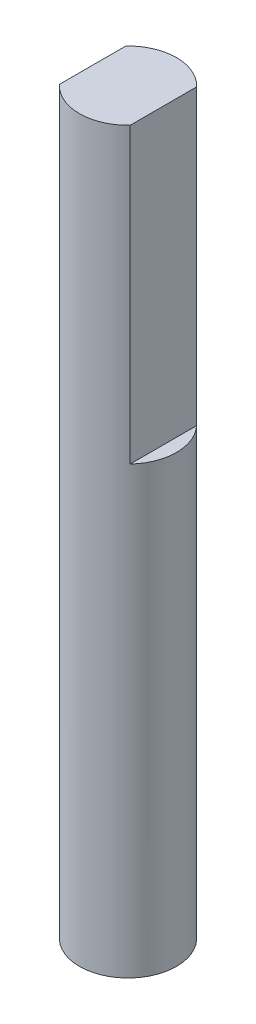
SolidWorks part; units mm, degrees
material "ABS"
ref_plane "Alzado" through (0, 0, 0) normal (0, 0, 1) x (1, 0, 0)
ref_plane "Planta" through (0, 0, 0) normal (0, 1, 0) x (1, 0, 0)
ref_plane "Vista lateral" through (0, 0, 0) normal (1, 0, 0) x (0, 0, -1)
sketch "Croquis2" plane through (0, 0, 0) normal (0, 1, 0) x (1, 0, 0)
  circle A0 centre (0, 0) radius 2.4
  dimension "D1" = 4.8
extrude "Saliente-Extruir1" add sketch "Croquis2" along normal mid plane 36.5
sketch "Croquis3" plane through (0, 18.25, 0) normal (0, 1, 0) x (1, 0, 0)
  line L0 (0, 0) -> (0, 2.4) construction
  line L1 (-1.75, 1.6424) -> (-1.75, -1.6424)
  line L2 (1.75, 1.6424) -> (1.75, -1.6424)
  circle A0 centre (0, 0) radius 2.4 construction
  arc A1 (-1.75, -1.6424) -> (1.75, -1.6424) centre (0, 0) ccw
  arc A2 (1.75, 1.6424) -> (-1.75, 1.6424) centre (0, 0) ccw
  dimension "D1" = 3.5
extrude "Cortar-Extruir-Lámina1" cut sketch "Croquis3" against normal blind 14.5 thin thin type one direction wall 10
